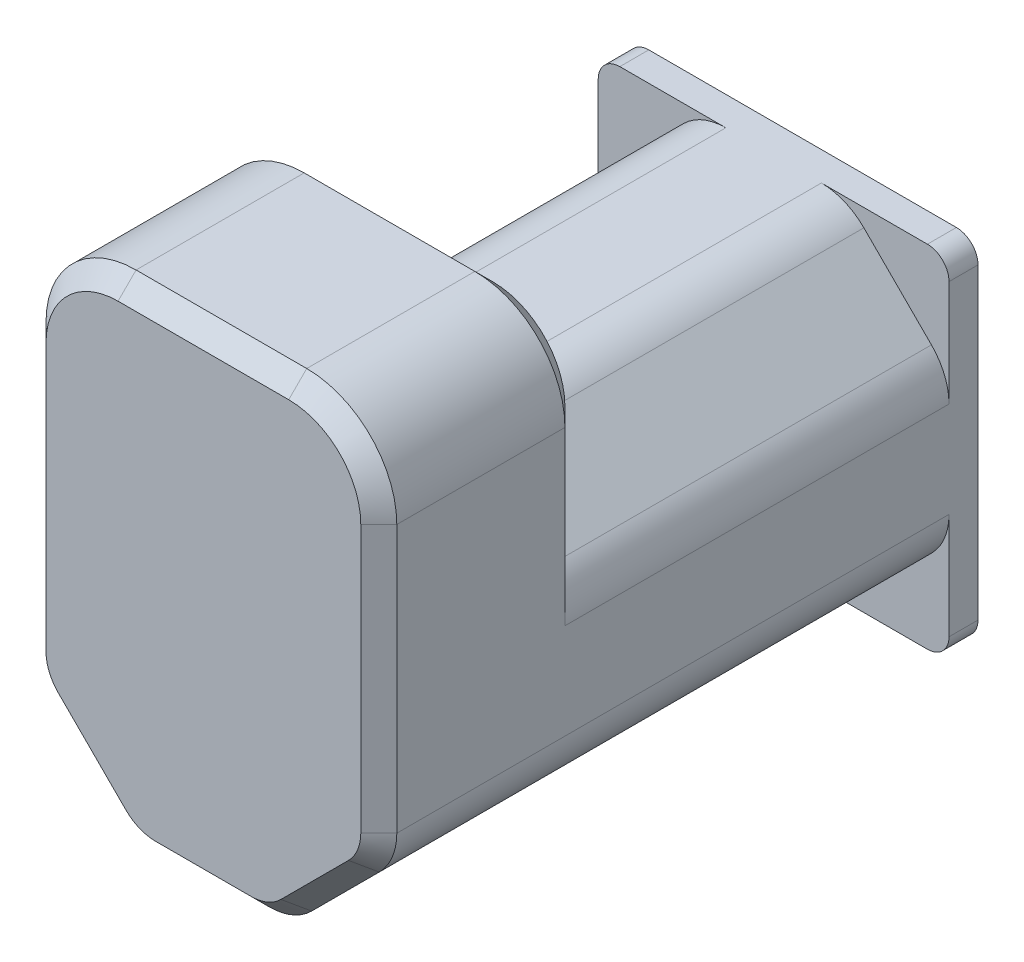
SolidWorks part; units mm, degrees
ref_plane "Front Plane" through (0, 0, 0) normal (0, 0, 1) x (1, 0, 0)
ref_plane "Top Plane" through (0, 0, 0) normal (0, 1, 0) x (1, 0, 0)
ref_plane "Right Plane" through (0, 0, 0) normal (1, 0, 0) x (0, 0, -1)
sketch "Sketch1" plane through (0, 0, 0) normal (0, 0, 1) x (1, 0, 0)
  line L1 (-25.61, -29.21) -> (25.61, -29.21)
  line L2 (-29.21, -25.61) -> (-29.21, 25.61)
  line L3 (-25.61, 29.21) -> (25.61, 29.21)
  line L4 (29.21, -25.61) -> (29.21, 25.61)
  line L5 (-29.21, -29.21) -> (29.21, 29.21) construction
  line L6 (-29.21, 29.21) -> (29.21, -29.21) construction
  arc A0 (25.61, 29.21) -> (29.21, 25.61) centre (25.61, 25.61) cw
  arc A1 (25.61, -29.21) -> (29.21, -25.61) centre (25.61, -25.61) ccw
  arc A2 (-25.61, -29.21) -> (-29.21, -25.61) centre (-25.61, -25.61) cw
  arc A3 (-29.21, 25.61) -> (-25.61, 29.21) centre (-25.61, 25.61) cw
  point P0 (0, 0)
  dimension "D2" = 3.6
  dimension "D1" = 58.42
extrude "Boss-Extrude1" add sketch "Sketch1" along normal blind 4.826
sketch "Sketch2" plane through (0, 0, 4.826) normal (0, 0, 1) x (1, 0, 0)
  line L0 (-29.21, 25.61) -> (-29.21, -25.61) construction
  line L1 (-29.21, 12.0992) -> (-29.21, -12.0992)
  line L2 (-29.21, -12.0992) -> (-12.0992, -29.21)
  line L3 (-12.0992, -29.21) -> (12.0992, -29.21)
  line L4 (12.0992, -29.21) -> (29.21, -12.0992)
  line L5 (29.21, -12.0992) -> (29.21, 12.0992)
  line L6 (29.21, 12.0992) -> (12.0992, 29.21)
  line L7 (12.0992, 29.21) -> (-12.0992, 29.21)
  line L8 (-12.0992, 29.21) -> (-29.21, 12.0992)
  circle A0 centre (0, 0) radius 29.21 construction
extrude "Boss-Extrude2" add sketch "Sketch2" along normal blind 60.96
sketch "Sketch3" plane through (0, 0, 65.786) normal (0, 0, 1) x (1, 0, 0)
  line L0 (-12.0992, -29.21) -> (12.0992, -29.21) construction
  line L1 (-29.21, 12.0992) -> (-29.21, -12.0992)
  line L2 (-29.21, -12.0992) -> (-12.0992, -29.21)
  line L3 (-12.0992, -29.21) -> (12.0992, -29.21)
  line L4 (12.0992, -29.21) -> (29.21, -12.0992)
  line L5 (29.21, -12.0992) -> (29.21, 12.0992)
  line L6 (29.21, 12.0992) -> (12.0992, 29.21) construction
  line L7 (12.0992, 29.21) -> (-12.0992, 29.21) construction
  line L8 (-12.0992, 29.21) -> (-29.21, 12.0992) construction
  line L9 (29.21, 51.562) -> (-29.21, 51.562)
  line L10 (29.21, 51.562) -> (29.21, 12.0992)
  line L11 (29.21, 12.0992) -> (-29.21, 12.0992) construction
  line L12 (-29.21, 51.562) -> (-29.21, 12.0992)
  line L13 (29.21, 51.562) -> (-29.21, 12.0992) construction
  line L14 (29.21, 12.0992) -> (-29.21, 51.562) construction
  circle A0 centre (0, 0) radius 29.21 construction
  point P1 (0, 31.8306)
  dimension "D1" = 22.352
extrude "Boss-Extrude3" add sketch "Sketch3" along normal blind 34
fillet "Fillet1" radius 10 8 edges
fillet "Fillet2" radius 15 2 edges at (29.21, 51.562, 82.786) (-29.21, 51.562, 82.786)
sketch "Sketch4" plane through (0, 0, 0) normal (0, 0, -1) x (-1, 0, 0)
  circle A0 centre (0, 0) radius 4.75
  dimension "D1" = 9.5
extrude "Boss-Extrude4" add sketch "Sketch4" along normal blind 20.32
chamfer "Chamfer2" distance 3 angle 45 12 edges at (20.6546, -20.6546, 99.786) (28.4488, -11.7839, 99.786) (11.7839, -28.4488, 99.786) (29.21, 14.3025, 99.786) (0, -29.21, 99.786) (24.8166, 47.1686, 99.786) (-11.7839, -28.4488, 99.786) (0, 51.562, 99.786) (-20.6546, -20.6546, 99.786) (-24.8166, 47.1686, 99.786) (-28.4488, -11.7839, 99.786) (-29.21, 14.3025, 99.786)
sketch "Sketch5" plane through (0, 0, 0) normal (0, 0, -1) x (-1, 0, 0)
  circle A0 centre (0, 0) radius 19
  circle A1 centre (0, 0) radius 7.62
  dimension "D1" = 15.24
  dimension "D2" = 38
extrude "Boss-Extrude5" add sketch "Sketch5" along normal blind 1.25
chamfer "Chamfer3" distance 3 angle 45 5 edges at (24.8166, 47.1686, 65.786) (0, 51.562, 65.786) (-24.8166, 47.1686, 65.786)
